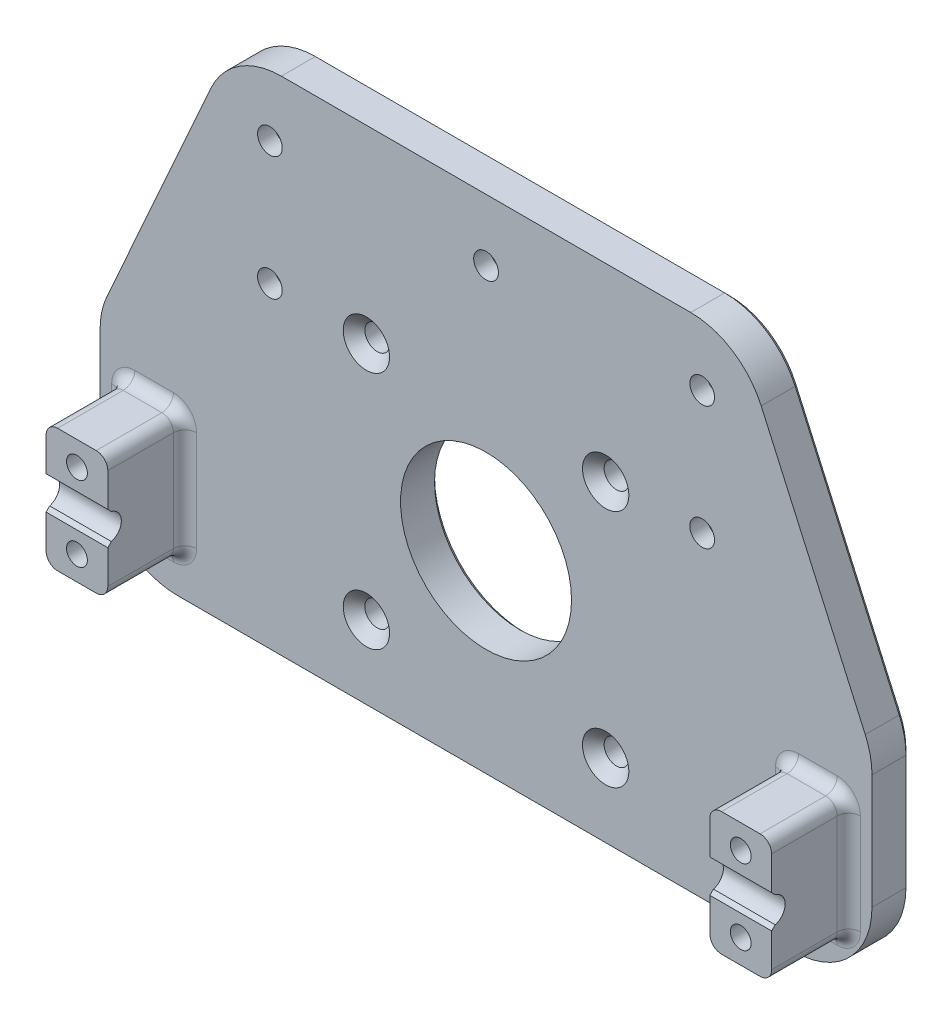
SolidWorks part; units mm, degrees
ref_plane "Front Plane" through (0, 0, 0) normal (0, 0, 1) x (1, 0, 0)
ref_plane "Top Plane" through (0, 0, 0) normal (0, 1, 0) x (1, 0, 0)
ref_plane "Right Plane" through (0, 0, 0) normal (1, 0, 0) x (0, 0, -1)
sketch "Sketch1" plane through (0, 0, 0) normal (0, 0, 1) x (1, 0, 0)
  line L1 (-50, -40) -> (50, -40)
  line L2 (-50, -40) -> (-50, 40)
  line L3 (-50, 40) -> (50, 40)
  line L4 (50, -40) -> (50, 40)
  line L5 (-50, -40) -> (50, 40) construction
  line L6 (-50, 40) -> (50, -40) construction
  point P0 (0, 0)
  dimension "D1" = 100
  dimension "D2" = 80
extrude "Boss-Extrude1" add sketch "Sketch1" along normal blind 5
sketch "Sketch2" plane through (0, 0, 5) normal (0, 0, 1) x (1, 0, 0)
  line L1 (15.5, -15.5) -> (-15.5, -15.5) construction
  line L2 (15.5, -15.5) -> (15.5, 15.5) construction
  line L3 (15.5, 15.5) -> (-15.5, 15.5) construction
  line L4 (-15.5, -15.5) -> (-15.5, 15.5) construction
  line L5 (15.5, -15.5) -> (-15.5, 15.5) construction
  line L6 (15.5, 15.5) -> (-15.5, -15.5) construction
  circle A0 centre (-15.5, 15.5) radius 1.6
  circle A1 centre (-15.5, -15.5) radius 1.6
  circle A2 centre (15.5, -15.5) radius 1.6
  circle A3 centre (15.5, 15.5) radius 1.6
  circle A4 centre (0, 0) radius 11.075
  point P0 (0, 0)
  dimension "D2" = 3.2
  dimension "D3" = 22.15
  dimension "D1" = 31
extrude "Cut-Extrude1" cut sketch "Sketch2" against normal blind 5
sketch "Sketch4" plane through (0, 0, 5) normal (0, 0, 1) x (1, 0, 0)
  line L0 (0, 0) -> (0, 32) construction
  line L1 (0, 32) -> (28, 32) construction
  circle A0 centre (28, 32) radius 1.6
  circle A1 centre (0, 32) radius 1.6
  circle A2 centre (-28, 32) radius 1.6
  circle A3 centre (28, 16) radius 1.6
  circle A4 centre (-28, 16) radius 1.6
  dimension "D3" = 3.2
  dimension "D4" = 3.2
  dimension "D5" = 16
  dimension "D1" = 32
  dimension "D2" = 28
extrude "Cut-Extrude2" cut sketch "Sketch4" against normal blind 18
sketch "Sketch5" plane through (0, 0, 5) normal (0, 0, 1) x (1, 0, 0)
  line L4 (-47, -20) -> (-39, -20)
  line L5 (-47, -20) -> (-47, -4)
  line L6 (-47, -4) -> (-39, -4)
  line L7 (-39, -20) -> (-39, -4)
  line L8 (-47, -20) -> (-39, -4) construction
  line L9 (-47, -4) -> (-39, -20) construction
  point P0 (-43, -12)
  dimension "D1" = 43
  dimension "D2" = 12
  dimension "D3" = 8
  dimension "D4" = 16
extrude "Boss-Extrude2" add sketch "Sketch5" along normal blind 10
sketch "Sketch6" plane through (-47, 0, 0) normal (-1, 0, 0) x (0, 0, 1)
  line L0 (15, -4) -> (15, -20) construction
  circle A0 centre (15, -12) radius 1.75
  dimension "D1" = 3.5
extrude "Cut-Extrude3" cut sketch "Sketch6" against normal blind 10
sketch "Sketch7" plane through (0, 0, 15) normal (0, 0, 1) x (1, 0, 0)
  line L0 (-43, -20) -> (-43, -13.75) construction
  line L1 (-47, -20) -> (-39, -20) construction
  line L2 (-39, -13.75) -> (-47, -13.75) construction
  line L3 (-43, -4) -> (-43, -10.25) construction
  line L4 (-39, -4) -> (-47, -4) construction
  line L5 (-47, -10.25) -> (-39, -10.25) construction
  circle A0 centre (-43, -16.875) radius 1.35
  circle A1 centre (-43, -7.125) radius 1.35
  dimension "D1" = 2.7
extrude "Cut-Extrude4" cut sketch "Sketch7" against normal blind 25
mirror "Mirror1" about plane through (0, 0, 0) normal (1, 0, 0) of "Boss-Extrude2", "Cut-Extrude3", "Cut-Extrude4"
sketch "Sketch8" plane through (0, 0, 5) normal (0, 0, 1) x (1, 0, 0)
  line L0 (-50, 40) -> (-50, -40) construction
  line L1 (50, -40) -> (-50, -40)
  line L2 (50, -40) -> (50, -25)
  line L3 (50, -25) -> (-50, -25)
  line L4 (-50, -40) -> (-50, -25)
  line L5 (-50, 2) -> (-33, 40)
  line L6 (50, 40) -> (-50, 40) construction
  line L7 (-33, 40) -> (-50, 40)
  line L8 (-50, 40) -> (-50, 2)
  line L9 (50, 2) -> (33, 40)
  line L10 (50, -40) -> (50, 40) construction
  line L11 (33, 40) -> (50, 40)
  line L12 (50, 40) -> (50, 2)
  dimension "D1" = 15
  dimension "D2" = 17
  dimension "D3" = 38
extrude "Cut-Extrude5" cut sketch "Sketch8" against normal through all both and the other way through all
fillet "Fillet1" radius 10 6 edges at (33, 40, 2.5) (50, 2, 2.5) (50, -25, 2.5) (-50, -25, 2.5) (-50, 2, 2.5) (-33, 40, 2.5)
fillet "Fillet2" radius 1.5 16 edges at (39, -12, 5) (-43, -4, 5) (43, -4, 5) (43, -20, 5) (-47, -12, 5) (-39, -12, 5) (39, -4, 10) (47, -4, 10) (39, -20, 10) (47, -12, 5) (47, -20, 10) (-43, -20, 5) (-47, -4, 10) (-47, -20, 10) (-39, -20, 10) (-39, -4, 10)
chamfer "Chamfer1" distance 0.6 angle 45 20 edges at (0, 40, 0) (31.9575, 38.3916, 0) (-31.9575, 38.3916, 0) (42.3875, 19.0162, 0) (-42.3875, 19.0162, 0) (49.7796, 1.953, 0) (-49.7796, 1.953, 0) (50, -7.5674, 0) (-50, -7.5674, 0) (47.0711, -22.0711, 0) (-47.0711, -22.0711, 0) (0, -25, 0) (17.1, 15.5, 0) (-13.9, 15.5, 0) (-44.35, -16.875, 0) (-44.35, -7.125, 0) (-13.9, -15.5, 0) (17.1, -15.5, 0) (41.65, -7.125, 0) (41.65, -16.875, 0)
chamfer "Chamfer2" distance 0.4 angle 45 4 edges at (43, -13.75, 15) (43, -10.25, 15) (-43, -13.75, 15) (-43, -10.25, 15)
chamfer "Chamfer3" distance 1.4 angle 45 4 edges at (17.1, 15.5, 5) (17.1, -15.5, 5) (-13.9, -15.5, 5) (-13.9, 15.5, 5)
chamfer "Chamfer4" distance 0.6 angle 45 1 edges at (11.075, 0, 0)
sketch "Croquis1" plane through (0, 0, 0) normal (0, 0, -1) x (-1, 0, 0)
  line L0 (0, 32) -> (0, 0) construction
  line L1 (-28, 28.7668) -> (-25.2, 30.3834)
  line L2 (-25.2, 30.3834) -> (-25.2, 33.6166)
  line L3 (-25.2, 33.6166) -> (-28, 35.2332)
  line L4 (-28, 35.2332) -> (-30.8, 33.6166)
  line L5 (-30.8, 33.6166) -> (-30.8, 30.3834)
  line L6 (-30.8, 30.3834) -> (-28, 28.7668)
  line L7 (-28, 12.7668) -> (-25.2, 14.3834)
  line L8 (-25.2, 14.3834) -> (-25.2, 17.6166)
  line L9 (-25.2, 17.6166) -> (-28, 19.2332)
  line L10 (-28, 19.2332) -> (-30.8, 17.6166)
  line L11 (-30.8, 17.6166) -> (-30.8, 14.3834)
  line L12 (-30.8, 14.3834) -> (-28, 12.7668)
  line L13 (0, 28.7668) -> (2.8, 30.3834)
  line L14 (2.8, 30.3834) -> (2.8, 33.6166)
  line L15 (2.8, 33.6166) -> (0, 35.2332)
  line L16 (0, 35.2332) -> (-2.8, 33.6166)
  line L17 (-2.8, 33.6166) -> (-2.8, 30.3834)
  line L18 (-2.8, 30.3834) -> (0, 28.7668)
  line L19 (30.8, 14.3834) -> (28, 12.7668)
  line L20 (30.8, 17.6166) -> (30.8, 14.3834)
  line L21 (28, 19.2332) -> (30.8, 17.6166)
  line L22 (25.2, 17.6166) -> (28, 19.2332)
  line L23 (25.2, 14.3834) -> (25.2, 17.6166)
  line L24 (28, 12.7668) -> (25.2, 14.3834)
  line L25 (30.8, 30.3834) -> (28, 28.7668)
  line L26 (30.8, 33.6166) -> (30.8, 30.3834)
  line L27 (28, 35.2332) -> (30.8, 33.6166)
  line L28 (25.2, 33.6166) -> (28, 35.2332)
  line L29 (25.2, 30.3834) -> (25.2, 33.6166)
  line L30 (28, 28.7668) -> (25.2, 30.3834)
  circle A0 centre (-28, 32) radius 2.8 construction
  circle A1 centre (-28, 16) radius 2.8 construction
  circle A2 centre (0, 32) radius 2.8 construction
  circle A3 centre (28, 16) radius 2.8 construction
  circle A4 centre (28, 32) radius 2.8 construction
  dimension "D1" = 5.6
extrude "Cortar-Extruir1" cut sketch "Croquis1" against normal blind 2.6
chamfer "Chaflán1" distance 0.4 angle 45 30 edges at (-29.4, 34.4249, 0) (-26.6, 34.4249, 0) (-25.2, 32, 0) (-26.6, 29.5751, 0) (-29.4, 29.5751, 0) (-30.8, 32, 0) (-29.4, 18.4249, 0) (-26.6, 18.4249, 0) (-25.2, 16, 0) (-26.6, 13.5751, 0) (-29.4, 13.5751, 0) (-30.8, 16, 0) (-1.4, 29.5751, 0) (-2.8, 32, 0) (-1.4, 34.4249, 0) (1.4, 34.4249, 0) (2.8, 32, 0) (1.4, 29.5751, 0) (26.6, 13.5751, 0) (25.2, 16, 0) (26.6, 18.4249, 0) (29.4, 18.4249, 0) (30.8, 16, 0) (29.4, 13.5751, 0) (26.6, 29.5751, 0) (25.2, 32, 0) (26.6, 34.4249, 0) (29.4, 34.4249, 0) (30.8, 32, 0) (29.4, 29.5751, 0)
sketch "Croquis2" plane through (0, 0, 2.6) normal (0, 0, -1) x (-1, 0, 0)
  line L0 (-30.8, 33.6166) -> (-30.8, 30.3834) construction
  line L1 (-30.8, 33.6166) -> (-25.2, 33.6166)
  line L2 (-30.8, 33.6166) -> (-30.8, 30.3834)
  line L3 (-30.8, 30.3834) -> (-25.2, 30.3834)
  line L4 (-25.2, 33.6166) -> (-25.2, 30.3834)
  line L6 (-30.8, 17.6166) -> (-25.2, 17.6166)
  line L7 (-30.8, 17.6166) -> (-30.8, 14.3834)
  line L8 (-30.8, 14.3834) -> (-25.2, 14.3834)
  line L9 (-25.2, 17.6166) -> (-25.2, 14.3834)
  line L10 (-2.8, 33.6166) -> (2.8, 33.6166)
  line L11 (-2.8, 33.6166) -> (-2.8, 30.3834)
  line L12 (-2.8, 30.3834) -> (2.8, 30.3834)
  line L13 (2.8, 33.6166) -> (2.8, 30.3834)
  line L14 (25.2, 17.6166) -> (30.8, 17.6166)
  line L15 (25.2, 17.6166) -> (25.2, 14.3834)
  line L16 (25.2, 14.3834) -> (30.8, 14.3834)
  line L17 (30.8, 17.6166) -> (30.8, 14.3834)
  line L18 (25.2, 33.6166) -> (30.8, 33.6166)
  line L19 (25.2, 33.6166) -> (25.2, 30.3834)
  line L20 (25.2, 30.3834) -> (30.8, 30.3834)
  line L21 (30.8, 33.6166) -> (30.8, 30.3834)
extrude "Cortar-Extruir2" cut sketch "Croquis2" against normal blind 0.2
